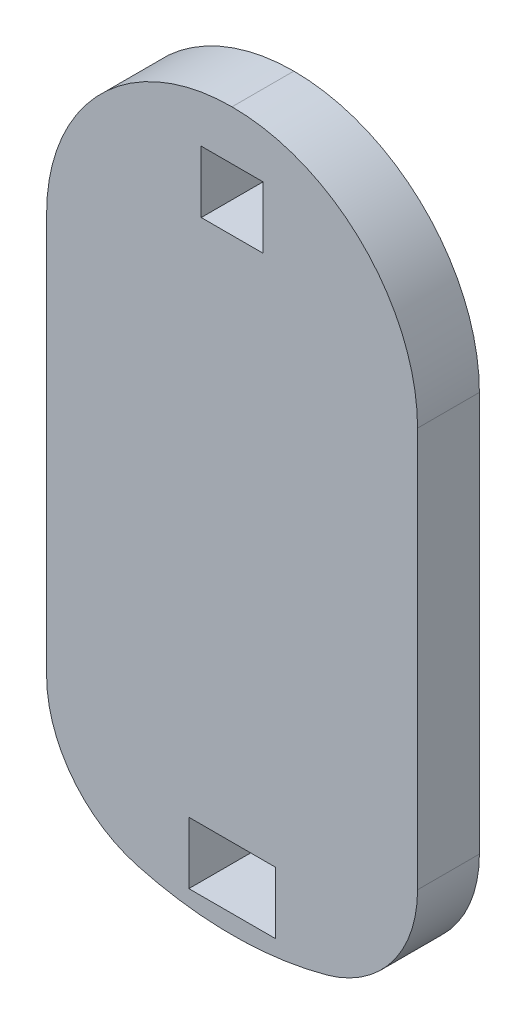
SolidWorks part; units mm, degrees
material "Acrylic (Medium-high impact)"
ref_plane "Front Plane" through (0, 0, 0) normal (0, 0, 1) x (1, 0, 0)
ref_plane "Top Plane" through (0, 0, 0) normal (0, 1, 0) x (1, 0, 0)
ref_plane "Right Plane" through (0, 0, 0) normal (1, 0, 0) x (0, 0, -1)
sketch "Sketch1" plane through (0, 0, 0) normal (0, 0, 1) x (1, 0, 0)
  circle A0 centre (0, 0) radius 29
  dimension "D1" = 58
extrude "Boss-Extrude1" add sketch "Sketch1" along normal blind 5
sketch "Sketch6" plane through (0, 0, 5) normal (0, 0, 1) x (1, 0, 0)
  line L0 (-15.0047, 24.8165) -> (-15.0047, -24.8165)
  line L1 (14.9953, 24.8222) -> (14.9953, -24.8222)
  arc A0 (-15.0047, 24.8165) -> (-15.0047, -24.8165) centre (0, 0) ccw
  circle A1 centre (0, 0) radius 29
  arc A2 (14.9953, -24.8222) -> (14.9953, 24.8222) centre (0, 0) ccw
  dimension "D2" = 15.0047
  dimension "D3" = 30
  dimension "D1" = 0
extrude "Cut-Extrude3" cut sketch "Sketch6" against normal blind 10
fillet "Fillet2" radius 15 2 edges at (-15.0047, 24.8165, 2.5) (14.9953, 24.8222, 2.5)
fillet "Fillet3" radius 10 2 edges at (-15.0047, -24.8165, 2.5) (14.9953, -24.8222, 2.5)
sketch "Sketch7" plane through (0, 0, 5) normal (0, 0, 1) x (1, 0, 0)
  line L1 (-2.5, 25) -> (2.5, 25)
  line L2 (-2.5, 25) -> (-2.5, 20)
  line L3 (-2.5, 20) -> (2.5, 20)
  line L4 (2.5, 25) -> (2.5, 20)
  line L5 (-3.5, -22.5) -> (3.5, -22.5)
  line L6 (-3.5, -22.5) -> (-3.5, -27.5)
  line L7 (-3.5, -27.5) -> (3.5, -27.5)
  line L8 (3.5, -22.5) -> (3.5, -27.5)
  point P9 (0, 25)
  point P11 (0, -22.5)
  dimension "D1" = 4
  dimension "D2" = 42.5
  dimension "D3" = 5
  dimension "D4" = 7
  dimension "D5" = 5
extrude "Cut-Extrude4" cut sketch "Sketch7" against normal blind 10
sketch "Sketch2" plane through (0, 0, 5) normal (0, 0, 1) x (1, 0, 0)
  line L1 (-5, 25) -> (5, 25)
  line L2 (-5, 25) -> (-5, 20)
  line L3 (-5, 20) -> (5, 20)
  line L4 (5, 25) -> (5, 20)
  line L5 (-5, 25) -> (5, 20) construction
  line L6 (-5, 20) -> (5, 25) construction
  point P0 (0, 22.5)
  dimension "D1" = 5
  dimension "D2" = 25
  dimension "D3" = 10
extrude "Boss-Extrude2" [suppressed] add sketch "Sketch2" along normal blind 38
sketch "Sketch3" [suppressed] plane through (0, 25, 0) normal (0, 1, 0) x (1, 0, 0)
  line L0 (5, -5) -> (-5, -5) construction
  line L1 (5, -43) -> (-5, -43) construction
  circle A0 centre (0, -12) radius 0.5
  circle A1 centre (0, -14) radius 0.5
  circle A2 centre (0, -16) radius 0.5
  circle A3 centre (0, -18) radius 0.5
  circle A4 centre (0, -20) radius 0.5
  circle A5 centre (0, -22) radius 0.5
  circle A6 centre (0, -40.5) radius 0.5
  circle A7 centre (0, -38.5) radius 0.5
  circle A8 centre (0, -36.5) radius 0.5
  circle A9 centre (0, -34.5) radius 0.5
  circle A10 centre (0, -32.5) radius 0.5
  circle A11 centre (0, -30.5) radius 0.5
  point P20 (0, -43)
  dimension "D2" = 1
  dimension "D5" = 8.5
  dimension "D6" = 2
  dimension "D1" = 7
  dimension "D7" = 2
  dimension "D3" = 6
  dimension "D4" = 6
extrude "Cut-Extrude1" [suppressed] cut sketch "Sketch3" against normal blind 5
sketch "Sketch4" [suppressed] plane through (0, 0, 5) normal (0, 0, 1) x (1, 0, 0)
  line L1 (-7.5, -22) -> (7.5, -22)
  line L2 (-7.5, -22) -> (-7.5, -27)
  line L3 (-7.5, -27) -> (7.5, -27)
  line L4 (7.5, -22) -> (7.5, -27)
  line L5 (-7.5, -22) -> (7.5, -27) construction
  line L6 (-7.5, -27) -> (7.5, -22) construction
  line L7 (-5, 20) -> (5, 20) construction
  point P0 (0, -24.5)
  dimension "D1" = 42
  dimension "D2" = 15
  dimension "D3" = 5
extrude "Boss-Extrude3" [suppressed] add sketch "Sketch4" along normal blind 32
sketch "Sketch5" [suppressed] plane through (0, -22, 0) normal (0, 1, 0) x (1, 0, 0)
  line L0 (-7.5, -5) -> (7.5, -5) construction
  circle A0 centre (0, -26.25) radius 3.8
  dimension "D1" = 21.25
  dimension "D2" = 7.6
extrude "Cut-Extrude2" [suppressed] cut sketch "Sketch5" against normal blind 28
fillet "Fillet4" [suppressed] radius 0.5
